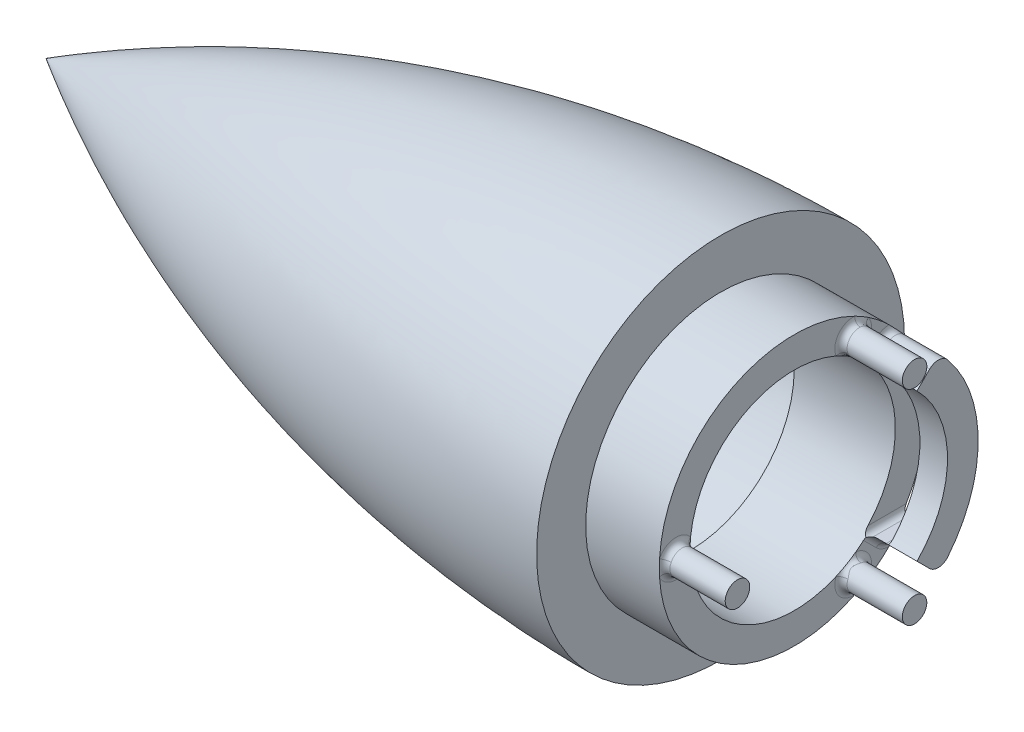
SolidWorks part; units mm, degrees
ref_plane "Front Plane" through (0, 0, 0) normal (0, 0, 1) x (1, 0, 0)
ref_plane "Top Plane" through (0, 0, 0) normal (0, 1, 0) x (1, 0, 0)
ref_plane "Right Plane" through (0, 0, 0) normal (1, 0, 0) x (0, 0, -1)
sketch "Sketch2" plane through (0, 0, 0) normal (0, 0, 1) x (1, 0, 0)
  line L0 (0, 216.6666) -> (0, 186.6666)
  line L3 (0, 186.6666) -> (-110, 186.6666)
  arc A1 (0, 216.6666) -> (-110, 186.6666) centre (0, 0) ccw
  point P1 (0, 216.6666)
  point P4 (0, 186.6666)
  dimension "D1" = 30
  dimension "D2" = 110
revolve "Revolve2" add sketch "Sketch2" angle 360 about L3
sketch "Sketch4" plane through (0, 0, 0) normal (1, 0, 0) x (0, 0, -1)
  circle A0 centre (0, 186.6666) radius 22
  dimension "D1" = 44
extrude "Boss-Extrude2" add sketch "Sketch4" along normal blind 20 contours A0
shell "Shell2" thickness 5 removed face at (20, 186.6666, -22)
sketch "Sketch14" plane through (0, 0, 0) normal (0, 0, 1) x (1, 0, 0)
  line L0 (0, 186.6666) -> (13.5, 186.6666)
  line L1 (0, 164.6666) -> (0, 208.6666) construction
  line L3 (15.5, 174.1666) -> (11.5, 174.1666)
  line L4 (15.5, 174.1666) -> (15.5, 199.1666)
  line L5 (15.5, 199.1666) -> (11.5, 199.1666)
  line L6 (11.5, 174.1666) -> (11.5, 199.1666)
  line L7 (15.5, 174.1666) -> (11.5, 199.1666) construction
  line L8 (15.5, 199.1666) -> (11.5, 174.1666) construction
extrude "Cut-Extrude5" cut sketch "Sketch14" against normal through all contours L6 L5 L4 L3
sketch "Sketch15" plane through (20, 0, 0) normal (1, 0, 0) x (0, 0, -1)
  line L1 (12.0208, 174.6458) -> (15.5563, 171.1103)
  line L2 (12.0208, 198.6874) -> (15.5563, 202.2229)
  circle A0 centre (0, 186.6666) radius 17 construction
  circle A1 centre (0, 186.6666) radius 22 construction
  arc A2 (12.0208, 198.6874) -> (12.0208, 174.6458) centre (0, 186.6666) ccw
  arc A3 (15.5563, 202.2229) -> (15.5563, 171.1103) centre (0, 186.6666) ccw
extrude "Cut-Extrude6" cut sketch "Sketch15" against normal blind 8
sketch "Sketch16" plane through (12, 0, 0) normal (1, 0, 0) x (0, 0, -1)
  line L0 (-20, 186.6666) -> (0, 186.6666)
  line L3 (10, 169.3461) -> (0, 186.6666)
  line L4 (0, 186.6666) -> (9.625, 203.3376)
  circle A0 centre (0, 186.6666) radius 22 construction
  circle A1 centre (0, 186.6666) radius 22
  circle A4 centre (9.625, 203.3376) radius 2
  circle A5 centre (9.625, 169.9956) radius 2
  circle A6 centre (-19.25, 186.6666) radius 2
  point P16 (0, 186.6666)
  dimension "D3" = 3
  dimension "D1" = 120
  dimension "D2" = 120
extrude "Boss-Extrude3" add sketch "Sketch16" along normal blind 10 contours A4 | A5 | A6 region at (12, 205.0207, -8.6533) region at (12, 171.6787, -10.5967) region at (12, 186.6666, 21.1934)
fillet "Fillet1" radius 1 2 edges at (15.5, 199.1666, -15.3019) (15.5, 174.1666, -15.3019)
fillet "Fillet2" radius 2 2 edges at (16, 202.2229, -15.5563) (16, 171.1103, -15.5563)
fillet "Fillet23" radius 1 5 edges at (11.5, 199.1666, -14.8128) (12, 199.9522, -13.2856) (12, 173.381, -13.2856) (12, 172.0121, -15.5856) (12, 201.3211, -15.5856)
fillet "Fillet27" radius 1 1 edges at (11.5, 174.1666, -14.8128)
fillet "Fillet28" radius 1 3 edges at (12, 169.9956, -11.625) (12, 203.3376, -11.625) (12, 186.6666, 17.25)
